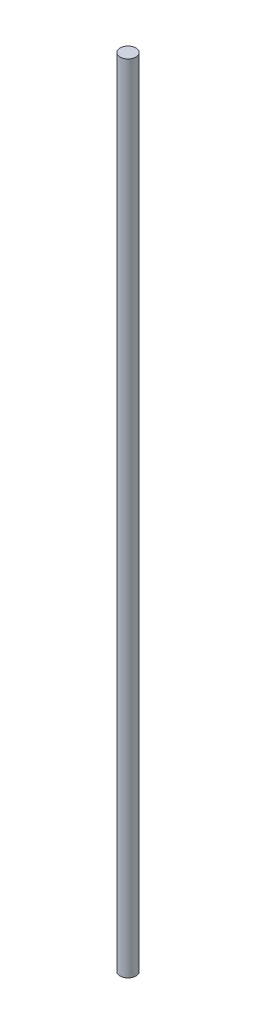
SolidWorks part; units mm, degrees
material "AISI 316 Annealed Stainless Steel Bar (SS)"
ref_plane "Front Plane" through (0, 0, 0) normal (0, 0, 1) x (1, 0, 0)
ref_plane "Top Plane" through (0, 0, 0) normal (0, 1, 0) x (1, 0, 0)
ref_plane "Right Plane" through (0, 0, 0) normal (1, 0, 0) x (0, 0, -1)
sketch "Sketch1" plane through (0, 0, 0) normal (0, 1, 0) x (1, 0, 0)
  circle A0 centre (0, 0) radius 4
  dimension "D1" = 8
extrude "Boss-Extrude1" add sketch "Sketch1" against normal blind 400
equation "\"rod_diameter\"= 8"
equation "\"rod_hole_thickness\"= 4"
equation "\"rod_radius\"= \"rod_diameter\" / 2"
equation "\"platter_diameter\"= 320"
equation "\"platter_radius\"= \"platter_diameter\" / 2"
equation "\"extruder_mount_hole_spacing\"= 75"
equation "\"arm_rod_spacing\"= 40"
equation "\"motor_level_rod_spacing\"= 15"
equation "\"linear_bearing_diameter\"= 15"
equation "\"z_rod_spacing\"= 75"
equation "\"platter_rod_spacing\"= 50"
equation "\"rod_nut_thickness\"= 6.5"
equation "\"rod_nut_inscribed_diameter\"= 13"
equation "\"z_height\"= 400"
equation "\"D1@Sketch1\"= \"rod_diameter\""
equation "\"D1@Boss-Extrude1\"= \"z_height\""
